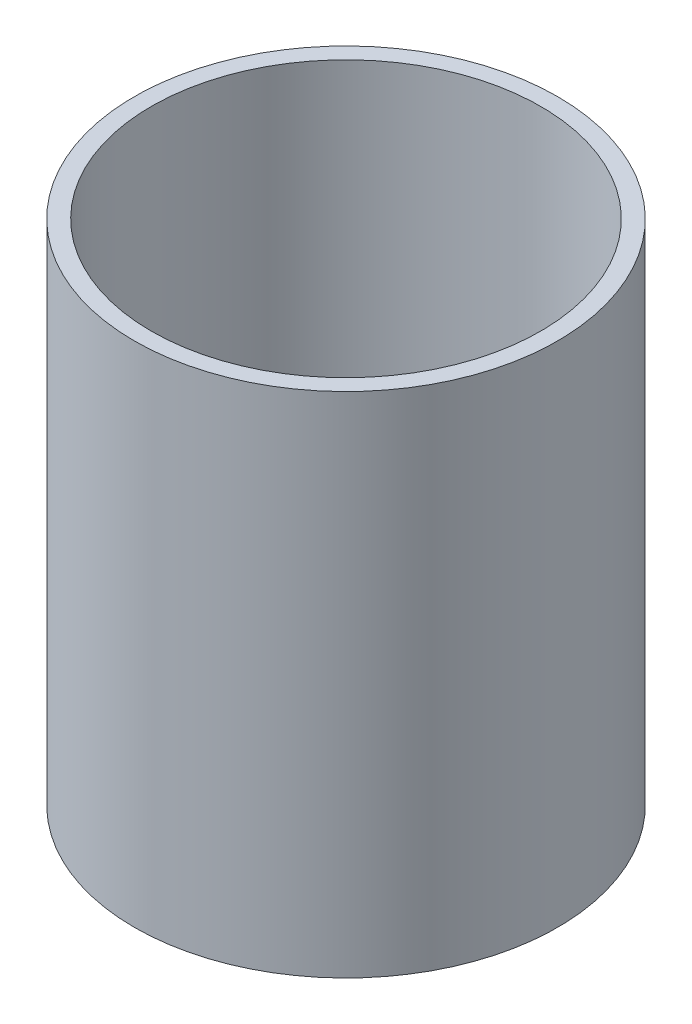
SolidWorks part; units mm, degrees
ref_plane "Front Plane" through (0, 0, 0) normal (0, 0, 1) x (1, 0, 0)
ref_plane "Top Plane" through (0, 0, 0) normal (0, 1, 0) x (1, 0, 0)
ref_plane "Right Plane" through (0, 0, 0) normal (1, 0, 0) x (0, 0, -1)
sketch "Sketch1" plane through (0, 0, 0) normal (0, 1, 0) x (1, 0, 0)
  circle A0 centre (0, 0) radius 1250
  circle A1 centre (0, 0) radius 1150
  circle A2 centre (0, 0) radius 1200 construction
  dimension "D1" = 2500
  dimension "D2" = 2400
  dimension "D3" = 2300
extrude "Boss-Extrude1" add sketch "Sketch1" along normal blind 3000
